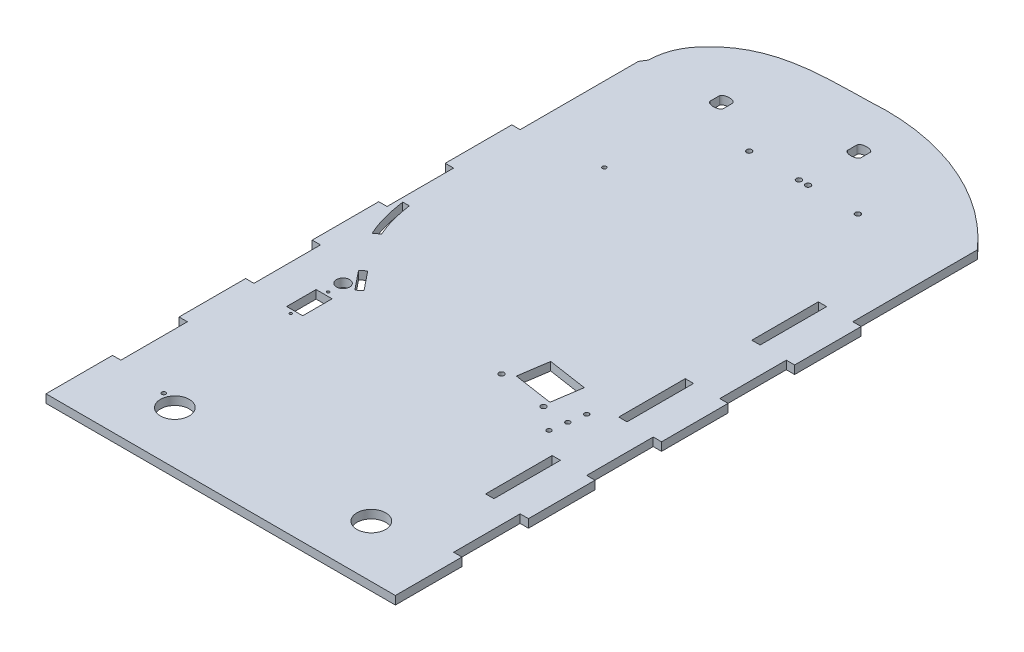
SolidWorks part; units mm, degrees
ref_plane "Front Plane" through (0, 0, 0) normal (0, 0, 1) x (1, 0, 0)
ref_plane "Top Plane" through (0, 0, 0) normal (0, 1, 0) x (1, 0, 0)
ref_plane "Right Plane" through (0, 0, 0) normal (1, 0, 0) x (0, 0, -1)
sketch "Sketch2" plane through (0, 0, 0) normal (0, 1, 0) x (1, 0, 0)
  line L0 (127, 0) -> (127, 40) construction
  line L1 (0, 0) -> (254, 0)
  line L2 (0, 0) -> (0, 508)
  line L3 (0, 508) -> (254, 508)
  line L4 (254, 0) -> (254, 508)
  line L5 (112, 0) -> (112, 40) construction
  line L6 (70.0293, 132.7246) -> (75.0014, 133.2514) construction
  line L8 (3.0464, 262.9295) -> (8.0974, 262.9295)
  line L9 (12.0177, 230.6311) -> (16.1196, 233.6878)
  line L10 (63.9635, 154.4733) -> (68.5195, 156.533) construction
  line L11 (31.3299, 200.9155) -> (35.2571, 204.0102)
  line L12 (42.9806, 186.4099) -> (46.8891, 189.5281)
  line L13 (27.8154, 172.0099) -> (40.0654, 172.0099)
  line L14 (27.8154, 172.0099) -> (27.8154, 149.5599)
  line L15 (40.0654, 172.0099) -> (40.0654, 149.5599)
  line L16 (27.8154, 149.5599) -> (40.0654, 149.5599)
  line L17 (0, 367.5) -> (57.0911, 367.5) construction
  line L20 (0, 358) -> (57.4432, 358) construction
  line L21 (57.0911, 367.5) -> (57.0911, 358) construction
  line L22 (138.65, 474.05) -> (138.65, 467.05) construction
  line L23 (148.65, 467.05) -> (148.65, 474.05) construction
  line L24 (138.65, 474.05) -> (138.65, 467.05)
  line L25 (148.65, 467.05) -> (148.65, 474.05)
  line L26 (63.65, 447.05) -> (63.65, 454.05) construction
  line L27 (53.65, 454.05) -> (53.65, 447.05) construction
  line L28 (63.65, 447.05) -> (63.65, 454.05)
  line L29 (53.65, 454.05) -> (53.65, 447.05)
  line L32 (195.0465, 209.5031) -> (191.6211, 186.7241)
  line L33 (191.6211, 186.7241) -> (161.4863, 191.2557)
  line L34 (161.4863, 191.2557) -> (164.9117, 214.0346)
  line L35 (164.9117, 214.0346) -> (195.0465, 209.5031)
  circle A0 centre (52, 40) radius 11
  circle A1 centre (202, 40) radius 11
  circle A2 centre (38.2469, 45.3329) radius 1.5
  circle A3 centre (34.0154, 186.4099) radius 5
  arc A4 (33.4154, 175.7599) -> (34.6154, 175.7599) centre (34.0154, 174.9599) ccw construction
  arc A5 (33.4154, 175.7599) -> (34.6154, 175.7599) centre (34.0154, 174.9599) ccw
  arc A6 (34.6154, 175.7599) -> (33.4154, 175.7599) centre (34.0154, 174.9599) ccw
  arc A7 (34.6154, 145.6599) -> (33.4154, 145.6599) centre (34.0154, 146.4599) ccw construction
  arc A8 (34.6154, 145.6599) -> (33.4154, 145.6599) centre (34.0154, 146.4599) ccw
  arc A9 (34.6154, 145.6599) -> (33.4154, 145.6599) centre (34.0154, 146.4599) cw
  circle A10 centre (57.0911, 362.75) radius 1.5
  circle A11 centre (184.6289, 428.7954) radius 2 construction
  circle A12 centre (146.6289, 428.7954) radius 2 construction
  circle A13 centre (139.6289, 428.7954) radius 2 construction
  circle A14 centre (101.6289, 428.7954) radius 2 construction
  circle A15 centre (184.6289, 428.7954) radius 2
  circle A16 centre (146.6289, 428.7954) radius 2
  circle A17 centre (139.6289, 428.7954) radius 2
  circle A18 centre (101.6289, 428.7954) radius 2
  circle A19 centre (154.4066, 187.01) radius 2 construction
  circle A20 centre (191.9904, 181.4011) radius 2 construction
  circle A21 centre (213.5907, 192.7999) radius 1.75 construction
  circle A22 centre (211.7247, 180.2964) radius 1.75 construction
  circle A23 centre (209.8587, 167.7928) radius 1.75 construction
  circle A24 centre (154.4066, 187.01) radius 2
  circle A25 centre (191.9904, 181.4011) radius 2
  circle A26 centre (213.5907, 192.7999) radius 1.75
  circle A27 centre (211.7247, 180.2964) radius 1.75
  circle A28 centre (209.8587, 167.7928) radius 1.75
  ellipse E0 centre (143.65, 474.05) end of major axis (138.65, 474.05) minor radius 2.5 (148.65, 474.05) -> (138.65, 474.05) ccw construction
  ellipse E1 centre (143.65, 467.05) end of major axis (138.65, 467.05) minor radius 2.5 (138.65, 467.05) -> (148.65, 467.05) ccw construction
  ellipse E2 centre (143.65, 467.05) end of major axis (138.65, 467.05) minor radius 2.5 (138.65, 467.05) -> (148.65, 467.05) ccw
  ellipse E3 centre (143.65, 474.05) end of major axis (138.65, 474.05) minor radius 2.5 (148.65, 474.05) -> (138.65, 474.05) ccw
  ellipse E4 centre (58.65, 447.05) end of major axis (63.65, 447.05) minor radius 2.5 (53.65, 447.05) -> (63.65, 447.05) ccw construction
  ellipse E5 centre (58.65, 454.05) end of major axis (63.65, 454.05) minor radius 2.5 (63.65, 454.05) -> (53.65, 454.05) ccw construction
  ellipse E6 centre (58.65, 447.05) end of major axis (63.65, 447.05) minor radius 2.5 (53.65, 447.05) -> (63.65, 447.05) ccw
  ellipse E7 centre (58.65, 454.05) end of major axis (63.65, 454.05) minor radius 2.5 (63.65, 454.05) -> (53.65, 454.05) ccw
  spline S0 degree 3 poles (0, 358) (10.2414, 318.2744) (-10.3205, 225.9555) (70.6512, 174.3118) (75.0014, 133.2514) knots 0 0 0 0 0.517006 1 1 1 1 construction
  spline S1 degree 3 poles (57.0275, 368.1055) (60.011, 340.8516) (38.8621, 298.2828) (61.0822, 235.4033) (84.5865, 206.7018) (104.9746, 198.8412) knots 0 0 0 0 0.426438 0.676001 1 1 1 1 construction
  spline S2 degree 1 poles (-4.8417, 356.7518) (70.0293, 132.7246) knots 0 0 1 1 construction
  spline S3 degree 3 poles (-4.8417, 356.7518) (-4.2453, 354.4384) (-3.2098, 349.8001) (-1.6146, 340.1963) (-0.4104, 327.7832) (0.2492, 312.4005) (0.7261, 291.8409) (1.4026, 275.812) (2.8811, 264.0829) (3.206, 261.7747) (3.5674, 259.4757) (3.9542, 257.1833) (4.5302, 254.1018) (5.5014, 249.6086) (6.6895, 245.0428) (8.2086, 240.135) (9.6429, 236.1559) (11.2633, 232.2426) (12.5555, 229.4544) (14.3601, 225.8497) (18.1885, 218.946) (23.3984, 211.2859) (29.2816, 203.4962) (32.93, 198.8824) (36.8298, 194.0373) (40.7355, 189.2215) (46.6866, 181.7864) (53.9965, 172.1125) (59.9683, 162.643) (63.1245, 156.3309) (64.1438, 154.0765) (64.4933, 153.279) (64.8362, 152.4792) (65.7137, 150.3629) (66.7102, 147.6655) (67.6191, 144.7625) (68.2641, 142.4625) (68.8611, 140.0122) (69.3531, 137.5307) (69.7433, 135.1238) (69.9343, 133.621) (70.0293, 132.7246) knots 0 0 0 0 0.03125 0.0625 0.125 0.1875 0.25 0.371368 0.378402 0.392471 0.399505 0.406539 0.420608 0.4375 0.462351 0.477976 0.5 0.513677 0.529302 0.537114 0.5625 0.625 0.649179 0.680429 0.696054 0.724459 0.755709 0.8125 0.875 0.898852 0.904562 0.907417 0.910272 0.915981 0.9375 0.948072 0.955885 0.96875 0.980913 0.988548 1 1 1 1 only from (0, 317.7537) to (70.0293, 132.7246) construction
  spline S4 degree 1 poles (35.2571, 204.0102) (46.8891, 189.5281) knots 0 0 1 1
  spline S5 degree 1 poles (31.3299, 200.9155) (42.9806, 186.4099) knots 0 0 1 1
  spline S6 degree 3 poles (3.0464, 262.9295) (4.6075, 251.8412) (7.2857, 240.8284) (12.0177, 230.6311) knots 0 0 0 0 1 1 1 1
  spline S7 degree 3 poles (8.0974, 262.9295) (9.5523, 252.911) (11.965, 242.952) (16.1196, 233.6878) knots 0 0 0 0 1 1 1 1
  spline S8 degree 3 poles (68.5195, 156.533) (70.3934, 152.3928) (73.1628, 144.7538) (74.6292, 136.7727) (75.0014, 133.2514) knots 0 0 0 0 0.562151 1 1 1 1 construction
  spline S9 degree 3 poles (63.9635, 154.4733) (65.5406, 150.9864) (68.1883, 143.8779) (69.6381, 136.4314) (70.0293, 132.7246) knots 0 0 0 0 0.506681 1 1 1 1 construction
  dimension "D3" = 22
  dimension "D9" = 3
  dimension "D10" = 3
  dimension "D1" = 508
  dimension "D2" = 254
  dimension "D4" = 40
  dimension "D5" = 15
  dimension "D6" = 60
  dimension "D7" = 150
  dimension "D8" = 5
extrude "Boss-Extrude1" add sketch "Sketch2" along normal blind 6.35
sketch "Sketch3" plane through (0, 6.35, 0) normal (0, 1, 0) x (1, 0, 0)
  line L0 (127, 508) -> (127, 338.6667) construction
  line L1 (254, 508) -> (0, 508) construction
  line L2 (127, 338.6667) -> (127, 169.3333) construction
  line L3 (127, 169.3333) -> (127, 0) construction
  line L4 (0, 0) -> (254, 0) construction
  line L5 (254, 0) -> (254, 508) construction
  line L6 (254, 508) -> (127, 508)
  line L7 (254, 450.6701) -> (254, 508)
  arc A1 (127, 508) -> (254, 450.6701) centre (127, 338.6667) cw
extrude "Cut-Extrude1" cut sketch "Sketch3" against normal up to next
sketch "Sketch5" plane through (0, 6.35, 0) normal (0, 1, 0) x (1, 0, 0)
  line L0 (254, 450.6701) -> (0, 450.6701) construction
  line L1 (0, 508) -> (0, 0) construction
  line L2 (3, 450.6701) -> (0, 445.8071)
  line L3 (0, 508) -> (0, 445.8071)
  line L6 (0, 508) -> (0, 526.7662)
  line L7 (0, 526.7662) -> (127, 526.7662)
  line L8 (127, 508) -> (127, 526.7662)
  circle A0 centre (45, 450.6701) radius 22 construction
  arc A2 (16.9934, 481.9692) -> (3, 450.6701) centre (45, 450.6701) ccw
  circle A3 centre (45, 450.6701) radius 42 construction
  spline S0 degree 3 poles (16.9934, 481.9692) (44.7711, 511.7661) (91.2093, 505.8566) (127, 508) knots 0 0 0 0 1 1 1 1
  dimension "D1" = 44
  dimension "D3" = 45
  dimension "D2" = 20
extrude "Cut-Extrude2" cut sketch "Sketch5" against normal up to next
sketch "Sketch7" plane through (0, 0, 0) normal (0, -1, 0) x (1, 0, 0)
  line L1 (254, 0) -> (260.35, 0)
  line L2 (254, 0) -> (254, -50.8)
  line L3 (254, -50.8) -> (260.35, -50.8)
  line L4 (260.35, 0) -> (260.35, -50.8)
  line L5 (0, 0) -> (-6.35, 0)
  line L6 (0, 0) -> (0, -50.8)
  line L7 (0, -50.8) -> (-6.35, -50.8)
  line L8 (-6.35, 0) -> (-6.35, -50.8)
  dimension "D1" = 6.35
  dimension "D2" = 50.8
  dimension "D3" = 6.35
  dimension "D4" = 50.8
extrude "Boss-Extrude2" add sketch "Sketch7" against normal up to surface (6.35 mm away) up to face at (209.8587, 6.35, -166.0428)
pattern_linear "LPattern1" count 4 spacing 101.6 along (0, 0, -1) of "Boss-Extrude2"
sketch "Sketch8" plane through (0, 6.35, 0) normal (0, 1, 0) x (1, 0, 0)
  line L0 (254, 152.4) -> (254, 203.2) construction
  line L5 (234, 152.4) -> (227.65, 152.4)
  line L7 (234, 152.4) -> (234, 101.6)
  line L9 (234, 101.6) -> (227.65, 101.6)
  line L10 (227.65, 152.4) -> (227.65, 101.6)
  line L11 (254, 101.6) -> (260.35, 101.6) construction
  line L12 (260.35, 101.6) -> (260.35, 152.4) construction
  dimension "D1" = 20
extrude "Cut-Extrude3" cut sketch "Sketch8" against normal up to next
pattern_linear "LPattern2" count 3 spacing 101.6 along (0, 0, -1) of "Cut-Extrude3"
sketch "Slider" plane through (0, 6.35, 6.35) normal (0, 1, 0) x (1, 0, 0)
  line L0 (0, 452.1571) -> (0, 361.95) construction
  line L6 (54.1176, 177.8402) -> (58.2442, 180.6634) construction
  spline S0 degree 3 poles (0, 364.2407) (10.0932, 324.5031) (-6.7408, 249.3382) (44.5453, 200.6868) (58.2442, 180.6634) knots 0 0 0 0 0.63201 1 1 1 1 construction
  spline S1 degree 3 poles (57.0275, 368.1055) (60.011, 340.8516) (38.8621, 298.2828) (61.0822, 235.4033) (84.5865, 206.7018) (104.9746, 198.8412) knots 0 0 0 0 0.426438 0.676001 1 1 1 1 construction
  spline S2 degree 1 poles (-4.8461, 363.0098) (54.1176, 177.8402) knots 0 0 1 1 construction
  spline S3 degree 3 poles (-4.8461, 363.0098) (-4.3659, 361.1191) (-3.5097, 357.3301) (-2.1229, 349.5349) (-0.9477, 339.5089) (-0.1716, 327.1083) (0.3662, 310.2426) (0.7835, 288.8153) (2.7416, 267.6076) (6.4419, 251.188) (10.6067, 239.2328) (16.4686, 227.9252) (23.4848, 217.3517) (31.2063, 207.235) (39.1962, 197.3973) (45.7189, 189.2885) (50.658, 182.7615) (52.9812, 179.5011) (54.1176, 177.8402) knots 0 0 0 0 0.03125 0.0625 0.125 0.1875 0.25 0.375 0.5 0.5625 0.625 0.6875 0.75 0.8125 0.875 0.9375 0.96875 1 1 1 1 only from (0, 321.3493) to (54.1176, 177.8402) construction
  dimension "D8" = 5
